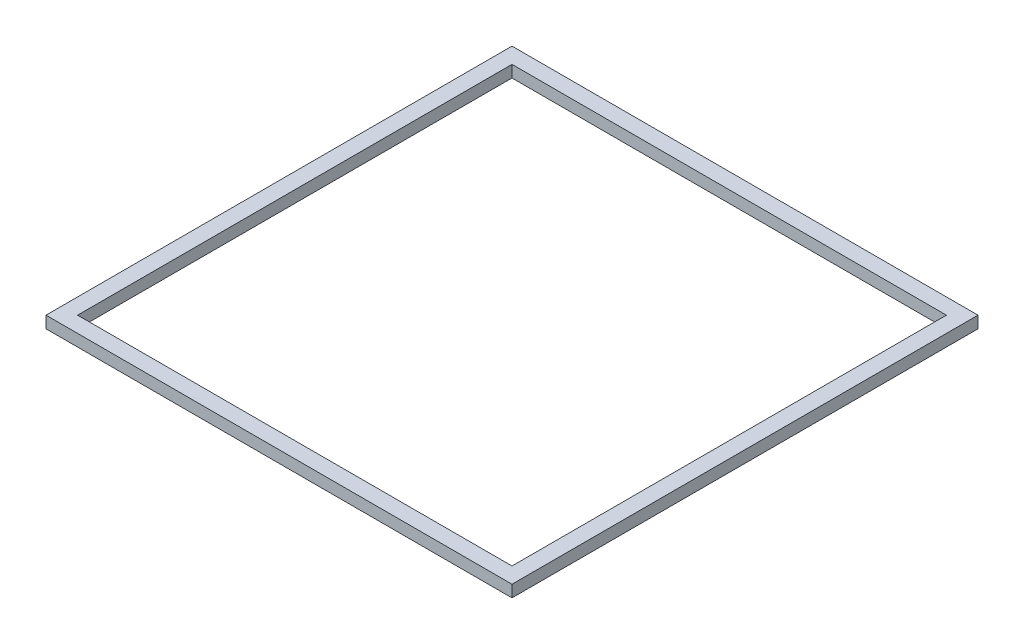
SolidWorks part; units mm, degrees
material "Concreto"
ref_plane "Plano frontal" through (0, 0, 0) normal (0, 0, 1) x (1, 0, 0)
ref_plane "Plano superior" through (0, 0, 0) normal (0, 1, 0) x (1, 0, 0)
ref_plane "Plano direito" through (0, 0, 0) normal (1, 0, 0) x (0, 0, -1)
sketch "Esboço1" plane through (0, 0, 0) normal (0, 1, 0) x (1, 0, 0)
  line L5 (-2750, 2750) -> (2750, 2750)
  line L6 (-2750, 2750) -> (-2750, -2750)
  line L11 (-2750, -2750) -> (2750, -2750)
  line L12 (2750, 2750) -> (2750, -2750)
  line L13 (-2750, 2750) -> (2750, -2750) construction
  line L14 (-2750, -2750) -> (2750, 2750) construction
  line L15 (-2950, 2950) -> (2950, 2950)
  line L16 (-2950, 2950) -> (-2950, -2950)
  line L17 (-2950, -2950) -> (2950, -2950)
  line L18 (2950, 2950) -> (2950, -2950)
  line L19 (-2950, 2950) -> (2950, -2950) construction
  line L20 (-2950, -2950) -> (2950, 2950) construction
  point P0 (0, 0)
  point P6 (0, 0)
  dimension "D1" = 5500
  dimension "D2" = 5500
  dimension "D3" = 200
  dimension "D4" = 200
extrude "Ressalto-extrusão1" add sketch "Esboço1" along normal blind 150
sketch "Esboço2" plane through (0, 150, 0) normal (0, 1, 0) x (1, 0, 0)
  line L0 (-2950, 0) -> (2950, 0) construction
  line L1 (-2950, 2950) -> (-2950, -2950) construction
  line L2 (2950, -2950) -> (2950, 2950) construction
  line L3 (0, 2950) -> (0, -2950) construction
  line L4 (2950, 2950) -> (-2950, 2950) construction
  line L5 (-2950, -2950) -> (2950, -2950) construction
  line L6 (-2950, 2950) -> (-2750, 2750) construction
  line L7 (2950, 2950) -> (2750, 2750) construction
  line L8 (2950, -2950) -> (2750, -2750) construction
  line L9 (-2950, -2950) -> (-2750, -2750) construction
  line L10 (-2850, 2850) -> (2850, 2850) construction
  line L11 (-2750, 2750) -> (-2750, 0) construction
  line L12 (-2850, -2850) -> (2850, -2850) construction
  line L13 (-2750, 2750) -> (-2750, -2750) construction
  line L14 (-2750, 0) -> (-2750, -2750) construction
  line L15 (2750, 2750) -> (2750, 0) construction
  line L16 (2750, -2750) -> (2750, 2750) construction
  line L17 (2750, 0) -> (2750, -2750) construction
  line L18 (-2750, 2750) -> (0, 2750) construction
  line L19 (2750, 2750) -> (-2750, 2750) construction
  line L20 (0, 2750) -> (2750, 2750) construction
  point P32 (-2750, -1375)
  point P36 (-2750, 1375)
  point P40 (2750, -1375)
  point P41 (2750, 1375)
  point P42 (1375, 2750)
  point P46 (-1375, 2750)
ref_plane "Plano1" through (0, 0, -2850) normal (0, 0, 1) x (1, 0, 0)
sketch "Esboço4" plane through (0, 0, -2850) normal (0, 0, 1) x (1, 0, 0)
  line L0 (-2850, 150) -> (2850, 150) construction
  line L1 (-2850, 150) -> (2850, 150) construction
  line L2 (2850, 150) -> (2850, 2850) construction
  line L3 (-2850, 150) -> (-2850, 3250) construction
  line L4 (2850, 2850) -> (-2850, 2850) construction
  line L6 (-2850, 3250) -> (2850, 2850) construction
  line L7 (0, 3050) -> (-14.0351, 2850) construction
  line L8 (2850, 2250) -> (-2850, 2250) construction
  line L9 (2850, 2250) -> (2250, 2850) construction
  line L10 (-2850, 2250) -> (-1915.5738, 3184.4262) construction
  dimension "D1" = 2700
  dimension "D2" = 3100
  dimension "D3" = 2100
  dimension "D4" = 45
  dimension "D5" = 45
ref_plane "Plano2" through (0, 75, 0) normal (0, 1, 0) x (1, 0, 0)
